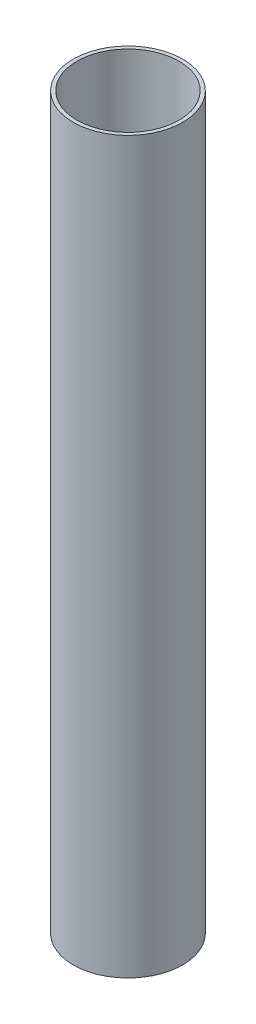
SolidWorks part; units mm, degrees
material "6061 Alloy"
ref_plane "Front Plane" through (0, 0, 0) normal (0, 0, 1) x (1, 0, 0)
ref_plane "Top Plane" through (0, 0, 0) normal (0, 1, 0) x (1, 0, 0)
ref_plane "Right Plane" through (0, 0, 0) normal (1, 0, 0) x (0, 0, -1)
sketch "Sketch1" plane through (0, 0, 0) normal (0, 1, 0) x (1, 0, 0)
  circle A0 centre (0, 0) radius 19.05
  circle A1 centre (0, 0) radius 17.78
  dimension "D1" = 38.1
  dimension "D2" = 35.56
extrude "Boss-Extrude1" add sketch "Sketch1" along normal blind 254
